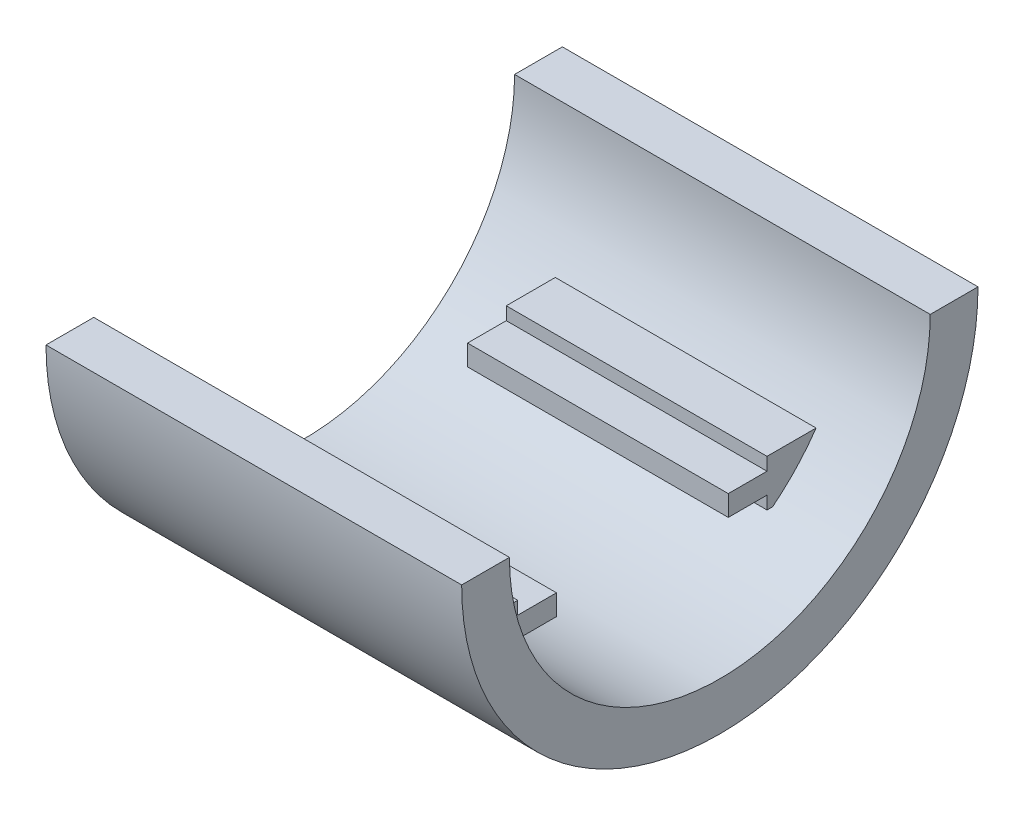
SolidWorks part; units mm, degrees
ref_plane "Front Plane" through (0, 0, 0) normal (0, 0, 1) x (1, 0, 0)
ref_plane "Top Plane" through (0, 0, 0) normal (0, 1, 0) x (1, 0, 0)
ref_plane "Right Plane" through (0, 0, 0) normal (1, 0, 0) x (0, 0, -1)
sketch "Sketch1" plane through (0, 0, 0) normal (0, 1, 0) x (1, 0, 0)
  line L1 (0, 0) -> (40.894, 0)
  line L2 (0, 0) -> (0, -25.4)
  line L3 (0, -25.4) -> (40.894, -25.4)
  line L4 (40.894, 0) -> (40.894, -25.4)
  dimension "D1" = 40.894
  dimension "D2" = 25.4
revolve "Revolve1" add sketch "Sketch1" angle 180 about L1
sketch "Sketch2" plane through (0, 0, 0) normal (0, 1, 0) x (1, 0, 0)
  line L1 (0, 0) -> (41.402, 0)
  line L2 (0, 0) -> (0, -20.701)
  line L4 (41.402, 0) -> (41.402, -20.701)
  line L5 (1.27, -20.701) -> (40.132, -20.701)
  line L8 (1.27, -20.701) -> (0, -20.701)
  line L9 (40.132, -20.701) -> (41.402, -20.701)
  line L10 (0, 0) -> (0, -21.971) construction
  line L11 (0, -21.971) -> (41.402, -21.971) construction
  line L12 (41.402, 0) -> (41.402, -21.971) construction
  line L13 (1.27, -1.27) -> (40.132, -1.27) construction
  line L14 (40.132, -1.27) -> (40.132, -20.701) construction
  line L15 (1.27, -1.27) -> (1.27, -20.701) construction
  line L16 (0, -25.4) -> (40.894, -25.4) construction
  dimension "D1" = 1.27
revolve "Cut-Revolve1" cut sketch "Sketch2" angle 360 about L1
sketch "Sketch3" plane through (0, 0, 0) normal (0, 0, 1) x (1, 0, 0)
  line L0 (40.894, -20.701) -> (40.894, 0) construction
  line L1 (33.274, -11.684) -> (7.62, -11.684)
  line L2 (33.274, -11.684) -> (33.274, -16.256)
  line L3 (33.274, -16.256) -> (7.62, -16.256)
  line L4 (7.62, -11.684) -> (7.62, -16.256)
  line L5 (40.894, 0) -> (0, 0) construction
  dimension "D1" = 7.62
  dimension "D2" = 7.62
  dimension "D3" = 4.572
  dimension "D4" = 11.684
extrude "Boss-Extrude1" add sketch "Sketch3" along normal up to surface and the other way up to surface
sketch "Sketch4" plane through (0, -11.684, 0) normal (0, 1, 0) x (1, 0, 0)
  line L0 (33.274, -17.0885) -> (33.274, 17.0885) construction
  line L1 (33.274, -12.2625) -> (7.62, -12.2625)
  line L2 (33.274, -12.2625) -> (33.274, 12.2625)
  line L3 (33.274, 12.2625) -> (7.62, 12.2625)
  line L4 (7.62, -12.2625) -> (7.62, 12.2625)
  line L5 (7.62, -17.0885) -> (7.62, 17.0885) construction
  line L6 (33.274, -17.0885) -> (7.62, -17.0885) construction
  line L7 (33.274, 17.0885) -> (7.62, 17.0885) construction
  dimension "D1" = 4.826
  dimension "D2" = 4.826
extrude "Cut-Extrude1" cut sketch "Sketch4" against normal blind 4.572
sketch "Sketch5" plane through (7.62, 0, 0) normal (-1, 0, 0) x (0, 0, 1)
  line L0 (-12.2625, -16.256) -> (-12.2625, -11.684) construction
  line L1 (-12.2625, -12.954) -> (-8.4525, -12.954)
  line L2 (-12.2625, -12.954) -> (-12.2625, -14.986)
  line L3 (-12.2625, -14.986) -> (-8.4525, -14.986)
  line L4 (-8.4525, -12.954) -> (-8.4525, -14.986)
  line L5 (12.2625, -16.256) -> (12.2625, -11.684) construction
  line L6 (12.2625, -12.954) -> (8.4525, -12.954)
  line L7 (12.2625, -12.954) -> (12.2625, -14.986)
  line L8 (12.2625, -14.986) -> (8.4525, -14.986)
  line L9 (8.4525, -12.954) -> (8.4525, -14.986)
  line L10 (17.0885, -11.684) -> (12.2625, -11.684) construction
  line L11 (-12.2625, -11.684) -> (-17.0885, -11.684) construction
  dimension "D1" = 2.032
  dimension "D2" = 3.81
  dimension "D3" = 1.27
  dimension "D4" = 1.27
  dimension "D5" = 2.032
  dimension "D6" = 3.81
extrude "Boss-Extrude2" add sketch "Sketch5" against normal up to surface (25.654 mm away) up to face at (33.274, -14.0106, -13.651)
sketch "Sketch6" plane through (0, 0, 0) normal (0, 1, 0) x (1, 0, 0)
  line L0 (40.894, -20.701) -> (0, -20.701) construction
  line L1 (7.112, -20.701) -> (11.684, -20.701)
  line L2 (7.112, -20.701) -> (7.112, -35.941)
  line L3 (7.112, -35.941) -> (11.684, -35.941)
  line L4 (11.684, -20.701) -> (11.684, -35.941)
  line L5 (0, -25.4) -> (0, -20.701) construction
  line L6 (29.21, -20.701) -> (33.782, -20.701)
  line L7 (29.21, -20.701) -> (29.21, -35.941)
  line L8 (29.21, -35.941) -> (33.782, -35.941)
  line L9 (33.782, -20.701) -> (33.782, -35.941)
  line L10 (40.894, -20.701) -> (40.894, -25.4) construction
  dimension "D1" = 7.112
  dimension "D2" = 7.112
  dimension "D3" = 4.572
  dimension "D4" = 4.572
  dimension "D5" = 15.24
  dimension "D6" = 15.24
extrude "Boss-Extrude3" [suppressed] add sketch "Sketch6" along normal blind 10.16
sketch "Sketch7" [suppressed] plane through (33.782, 0, 0) normal (1, 0, 0) x (0, 0, -1)
  line L0 (-35.941, 10.16) -> (-20.701, 10.16) construction
  line L5 (-35.941, 10.16) -> (-35.941, 0) construction
  circle A2 centre (-30.861, 5.08) radius 2.54
  dimension "D3" = 5.08
  dimension "D1" = 5.08
  dimension "D2" = 5.08
extrude "Cut-Extrude2" [suppressed] cut sketch "Sketch7" against normal blind 34.036
fillet "Fillet6" [suppressed] type full round
fillet "Fillet7" [suppressed] type full round
fillet "Fillet8" [suppressed] radius 5.08
